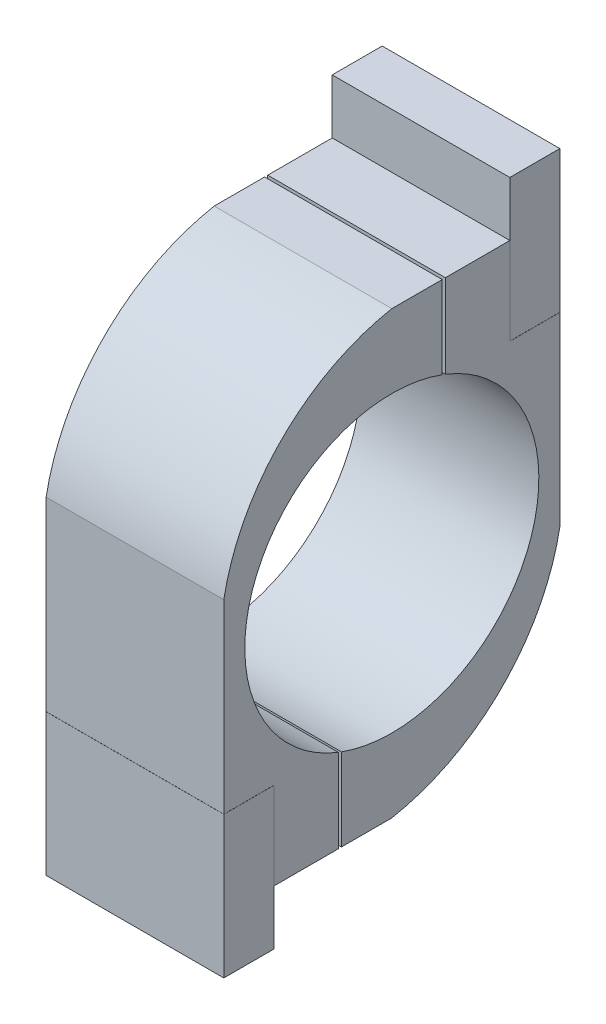
SolidWorks part; units mm, degrees
ref_plane "Front Plane" through (0, 0, 0) normal (0, 0, 1) x (1, 0, 0)
ref_plane "Top Plane" through (0, 0, 0) normal (0, 1, 0) x (1, 0, 0)
ref_plane "Right Plane" through (0, 0, 0) normal (1, 0, 0) x (0, 0, -1)
sketch "Sketch2" plane through (0, 0, 0) normal (1, 0, 0) x (0, 0, -1)
  point P0 (-4.302, -28.2499)
  line B0 (-11.2375, -26.2732) -> (-11.2375, -12.7732)
  line B1 (-11.2375, -12.7732) -> (-16, -12.7732)
  line B2 (-16, -12.7732) -> (-16, -26.2732)
  line B3 (-16, -26.2732) -> (-11.2375, -26.2732)
  line B4 (4.8, 13.078) -> (4.8, 20.9266)
  line B5 (4.8, 20.9266) -> (0, 20.9266)
  line B6 (-16, 4.9266) -> (-16, -12.7634)
  line B7 (-16, -12.7634) -> (-11.2375, -12.7634)
  line B8 (-11.2375, -12.7634) -> (-11.2375, -21.0734)
  line B9 (-11.2375, -21.0734) -> (-5.1, -21.0734)
  line B10 (-5.1, -21.0734) -> (-5.1, -13.1114)
  line B11 (11.2375, 26.1264) -> (11.2375, 12.6264)
  line B12 (11.2375, 12.6264) -> (16, 12.6264)
  line B13 (16, 12.6264) -> (16, 26.1264)
  line B14 (16, 26.1264) -> (11.2375, 26.1264)
  line B15 (-4.8, -13.2248) -> (-4.8, -21.0734)
  line B16 (-4.8, -21.0734) -> (0, -21.0734)
  line B17 (16, -5.0734) -> (16, 12.6166)
  line B18 (16, 12.6166) -> (11.2375, 12.6166)
  line B19 (11.2375, 12.6166) -> (11.2375, 20.9266)
  line B20 (11.2375, 20.9266) -> (5.1, 20.9266)
  line B21 (5.1, 20.9266) -> (5.1, 12.9646)
  arc B22 (4.8, 13.078) -> (0, 13.9266) centre (0, -0.0734) ccw
  arc B23 (0, 20.9266) -> (-16, 4.9266) centre (3.6619, 1.2647) ccw
  arc B24 (0, 13.9266) -> (-5.1, -13.1114) centre (0, -0.0734) ccw
  arc B25 (-4.8, -13.2248) -> (0, -14.0734) centre (0, -0.0734) ccw
  arc B26 (0, -21.0734) -> (16, -5.0734) centre (-3.6619, -1.4115) ccw
  arc B27 (0, -14.0734) -> (5.1, 12.9646) centre (0, -0.0734) ccw
sketch_block_instance "Block-Weapon-1"
sketch_block "Block-Weapon"
extrude "Boss-Extrude1" add sketch "Sketch2" along normal mid plane 16.9164 contours B27 B25 B15 B16 B26 B17 B18 B19 B11 B20 B21 region at (0, 16.7765, -10.7688)
extrude "Boss-Extrude2" add sketch "Sketch2<4>" along normal mid plane 16.9164 separate body contours B24 B22 B4 B5 B23 B6 B7 B8 B0 B9 B10 region at (0, -16.9233, 10.7688)
sketch "Sketch2<4>" plane through (0, 0, 0) normal (1, 0, 0) x (0, 0, -1) same geometry as "Sketch2"
extrude "Boss-Extrude3" add sketch "Sketch2<5>" along normal mid plane 16.9164 separate body contours B13 B14 B11 B12 region at (0, 19.3764, -13.6188)
sketch "Sketch2<5>" plane through (0, 0, 0) normal (1, 0, 0) x (0, 0, -1) same geometry as "Sketch2"
extrude "Boss-Extrude4" add sketch "Sketch2<6>" along normal mid plane 16.9164 separate body contours B2 B3 B0 B1 region at (0, -19.5232, 13.6187)
sketch "Sketch2<6>" plane through (0, 0, 0) normal (1, 0, 0) x (0, 0, -1) same geometry as "Sketch2"
